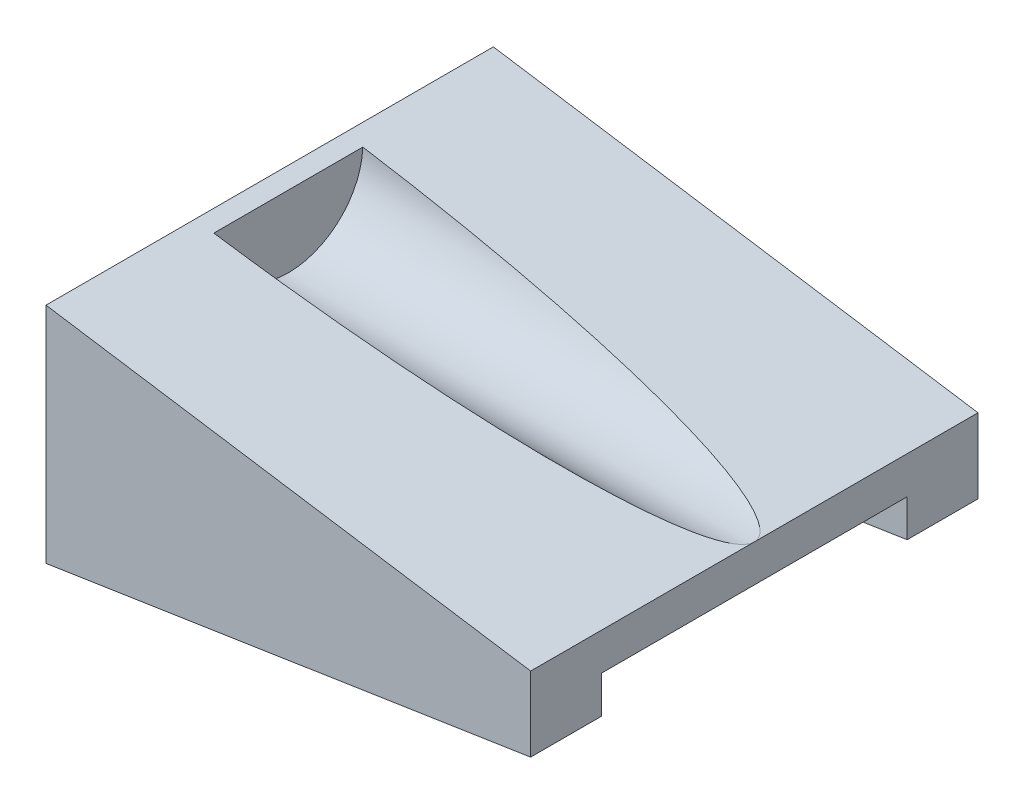
SolidWorks part; units mm, degrees
ref_plane "前视" through (0, 0, 0) normal (0, 0, 1) x (1, 0, 0)
ref_plane "上视" through (0, 0, 0) normal (0, 1, 0) x (1, 0, 0)
ref_plane "右视" through (0, 0, 0) normal (1, 0, 0) x (0, 0, -1)
sketch "Sketch1" plane through (0, 0, 0) normal (0, 1, 0) x (1, 0, 0)
  line L1 (-6.5, -6) -> (6.5, -6)
  line L2 (-6.5, -6) -> (-6.5, 6)
  line L3 (-6.5, 6) -> (6.5, 6)
  line L4 (6.5, -6) -> (6.5, 6)
  line L5 (-6.5, -6) -> (6.5, 6) construction
  line L6 (-6.5, 6) -> (6.5, -6) construction
  point P0 (0, 0)
  dimension "D1" = 12
  dimension "D2" = 13
extrude "Boss-Extrude1" add sketch "Sketch1" along normal blind 3
sketch "Sketch2" plane through (0, 0, 0) normal (0, -1, 0) x (1, 0, 0)
  line L0 (6.5, 6) -> (6.5, -6) construction
  line L1 (-6.5, 6) -> (6.5, 6)
  line L2 (-6.5, 6) -> (-6.5, 4.1)
  line L3 (-6.5, 4.1) -> (6.5, 4.1)
  line L4 (6.5, 6) -> (6.5, 4.1)
  line L6 (-6.5, -6) -> (6.5, -6)
  line L7 (-6.5, -6) -> (-6.5, -4.1)
  line L8 (-6.5, -4.1) -> (6.5, -4.1)
  line L9 (6.5, -6) -> (6.5, -4.1)
  dimension "D1" = 8.2
extrude "Boss-Extrude2" add sketch "Sketch2" along normal blind 3
chamfer "Chamfer1" distance 2 distance2 13 3 edges at (6.5, -3, 5.05) (6.5, -3, -5.05) (6.5, 3, 0) first distance on face at (6.5, -0.9375, 0.5125)
sketch "Sketch5" plane through (-6.5, 0, 0) normal (-1, 0, 0) x (0, 0, 1)
  line L0 (-6, 3) -> (6, 3) construction
  line L1 (-2, 3) -> (2, 3)
  arc A0 (-2, 3) -> (2, 3) centre (0, 3) ccw
  dimension "D1" = 4
extrude "Cut-Extrude1" cut sketch "Sketch5" against normal up to next from offset 0.5 offset against normal yes
